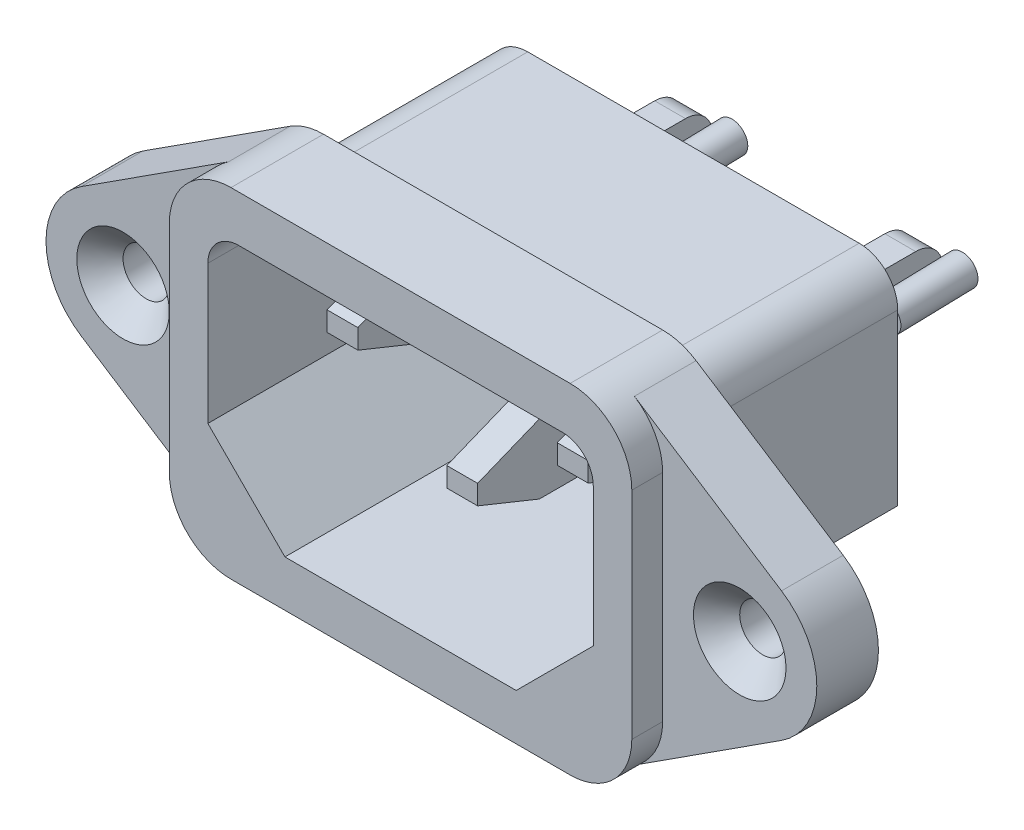
SolidWorks part; units mm, degrees
ref_plane "Front Plane" through (0, 0, 0) normal (0, 0, 1) x (1, 0, 0)
ref_plane "Top Plane" through (0, 0, 0) normal (0, 1, 0) x (1, 0, 0)
ref_plane "Right Plane" through (0, 0, 0) normal (1, 0, 0) x (0, 0, -1)
ref_plane "Plane1" through (0, 0, 0) normal (0, 0, -1) x (-1, 0, 0)
sketch "Sketch1" plane through (0, 0, 0) normal (0, 0, -1) x (-1, 0, 0)
  line L0 (-13.1694, 10.3606) -> (-22.7117, 4.2008)
  line L1 (-22.7117, -4.2008) -> (-13.1694, -10.3606)
  line L2 (-11, -11) -> (11, -11)
  line L3 (13.1694, -10.3606) -> (22.7117, -4.2008)
  line L4 (22.7117, 4.2008) -> (13.1694, 10.3606)
  line L5 (11, 11) -> (-11, 11)
  line L6 (0, 0) -> (-6.588, 0) construction
  line L7 (0, 0) -> (0, 5.2271) construction
  arc A0 (-22.7117, 4.2008) -> (-22.7117, -4.2008) centre (-20, 0) ccw
  arc A1 (-13.1694, -10.3606) -> (-11, -11) centre (-11, -7) ccw
  arc A2 (11, -11) -> (13.1694, -10.3606) centre (11, -7) ccw
  arc A3 (22.7117, -4.2008) -> (22.7117, 4.2008) centre (20, 0) ccw
  arc A4 (13.1694, 10.3606) -> (11, 11) centre (11, 7) ccw
  arc A5 (-11, 11) -> (-13.1694, 10.3606) centre (-11, 7) ccw
  point P18 (0, -11)
  point P22 (-25, 0)
  point P23 (25, 0)
  dimension "D3" = 5
  dimension "D4" = 4
  dimension "D1" = 22
  dimension "D2" = 50
  dimension "D5" = 40
extrude "Base" add sketch "Sketch1" against normal blind 4
sketch "Sketch2" plane through (0, 0, 4) normal (0, 0, 1) x (1, 0, 0)
  line L0 (11, -11) -> (-11, -11)
  line L1 (-15, -7) -> (-15, 7)
  line L2 (-11, 11) -> (11, 11)
  line L3 (15, 7) -> (15, -7)
  line L4 (-11, 11) -> (11, 11) construction
  line L5 (0, 0) -> (0, 5.1252) construction
  arc A0 (-11, -11) -> (-15, -7) centre (-11, -7) cw
  arc A1 (-15, 7) -> (-11, 11) centre (-11, 7) cw
  arc A2 (11, 11) -> (15, 7) centre (11, 7) cw
  arc A3 (15, -7) -> (11, -11) centre (11, -7) cw
  dimension "D3" = 4
  dimension "D1" = 30
  dimension "D2" = 22
extrude "Boss-Extrude2" add sketch "Sketch2" along normal blind 2
sketch "Sketch3" plane through (0, 0, 0) normal (0, 0, -1) x (-1, 0, 0)
  line L0 (13.25, -9.25) -> (-13.25, -9.25)
  line L1 (-13.25, -9.25) -> (-13.25, 9.25)
  line L2 (-13.25, 9.25) -> (13.25, 9.25)
  line L3 (13.25, 9.25) -> (13.25, -9.25)
  dimension "D1" = 26.5
  dimension "D2" = 18.5
extrude "Boss-Extrude3" add sketch "Sketch3" along normal blind 13
sketch "Sketch4" plane through (0, 0, 6) normal (0, 0, 1) x (1, 0, 0)
  line L0 (-12.5, -8) -> (12.5, -8)
  line L1 (12.5, -8) -> (12.5, 8)
  line L2 (12.5, 8) -> (-12.5, 8)
  line L3 (-12.5, 8) -> (-12.5, -8)
  line L4 (0, 4.6085) -> (0, 0) construction
  line L5 (0, 0) -> (4.1755, 0) construction
  dimension "D1" = 25
  dimension "D2" = 16
extrude "Cut-Extrude1" cut sketch "Sketch4" against normal blind 17
ref_plane "Plane2" through (1, 0, 0) normal (1, 0, 0) x (0, 0, -1)
sketch "Sketch5" plane through (1, 0, 0) normal (1, 0, 0) x (0, 0, -1)
  line L0 (2, 0.0009) -> (-3.5689, -2.2491)
  line L1 (-3.5689, -2.2491) -> (2, -4.4991)
  line L2 (2, -4.4991) -> (13, -4.4991)
  line L4 (13, 0.0009) -> (2, 0.0009)
  line L5 (13, 9.25) -> (13, -9.25) construction
  line L6 (-3.5689, -2.2491) -> (-0.3984, -2.2491) construction
  line L7 (13, 0.0009) -> (13, -0.6306)
  line L8 (13, -0.6306) -> (19.3815, -0.6306)
  line L9 (13, -4.4991) -> (13, -3.8676)
  line L10 (13, -3.8676) -> (19.3815, -3.8676)
  arc A0 (19.3815, -3.8676) -> (19.3815, -0.6306) centre (19.3815, -2.2491) ccw
  dimension "D1" = 8
  dimension "D2" = 3.2371
extrude "GND" add sketch "Sketch5" against normal blind 2
ref_plane "Plane3" through (-6.7672, 0, 0) normal (1, 0, 0) x (0, 0, -1)
sketch "Sketch6" plane through (-6.7672, 0, 0) normal (1, 0, 0) x (0, 0, -1)
  line L0 (2, 4.8652) -> (-3.5689, 2.6152)
  line L1 (-3.5689, 2.6152) -> (2, 0.3652)
  line L2 (2, 0.3652) -> (12.6657, 0.3652)
  line L3 (13, 9.25) -> (13, -9.25) construction
  line L4 (12.6657, 4.8652) -> (2, 4.8652)
  line L6 (12.6657, 4.8652) -> (12.6657, 4.3652)
  line L7 (12.6657, 4.3652) -> (19.25, 4.3652)
  line L8 (19.25, 0.8652) -> (12.6657, 0.8652)
  line L9 (12.6657, 0.8652) -> (12.6657, 0.3652)
  line L10 (-3.5689, 2.6152) -> (2.7205, 2.6152) construction
  arc A0 (19.25, 0.8652) -> (19.25, 4.3652) centre (19.25, 2.6152) ccw
  dimension "D1" = 3.5
  dimension "D2" = 8
extrude "L" add sketch "Sketch6" against normal blind 2
ref_plane "Plane4" through (8.1657, 0, 0) normal (1, 0, 0) x (0, 0, -1)
sketch "Sketch7" plane through (8.1657, 0, 0) normal (1, 0, 0) x (0, 0, -1)
  line L0 (2, 4.8652) -> (-3.5689, 2.6152)
  line L1 (-3.5689, 2.6152) -> (2, 0.3652)
  line L2 (2, 0.3652) -> (13, 0.3652)
  line L4 (13, 4.8652) -> (2, 4.8652)
  line L5 (13, 9.25) -> (13, -9.25) construction
  line L6 (13, 0.8652) -> (19.25, 0.8652) construction
  line L7 (19.25, 4.3652) -> (13, 4.3652) construction
  line L8 (13, 0.8652) -> (19.25, 0.8652)
  line L9 (19.25, 4.3652) -> (13, 4.3652)
  line L10 (13, 4.3652) -> (13, 4.8652)
  line L11 (13, 0.8652) -> (13, 0.3652)
  arc A0 (19.25, 0.8652) -> (19.25, 4.3652) centre (19.25, 2.6152) ccw construction
  arc A1 (19.25, 0.8652) -> (19.25, 4.3652) centre (19.25, 2.6152) ccw
extrude "N" add sketch "Sketch7" against normal blind 2
hole_wizard "Mount Ø3.0 (3) Diameter Hole1" positions "Sketch12" profile "Sketch11" hole size "Ø3.0" standard "ANSI Metric"
sketch "Sketch12" plane through (0, 0, 4) normal (0, 0, 1) x (1, 0, 0)
  point P0 (-20, 0)
  point P1 (20, 0)
sketch "Sketch11" plane through (-20, 0, 4) normal (1, 0, 0) x (0, -1, 0)
  line L0 (0, 0) -> (0, 25)
  line L1 (0, 25) -> (1.5, 25)
  line L2 (1.5, 25) -> (1.5, 0)
  line L5 (1.5, 0) -> (0, 0)
  line L11 (0, -6.35) -> (0, 107.95) construction
  dimension "Thru Hole Dia." = 3
  dimension "Thru Hole Depth" = 25
chamfer "Chamfer1" distance 5 angle 45 4 edges at (13.25, -9.25, -6.5) (-13.25, -9.25, -6.5) (12.5, -8, -2.5) (-12.5, -8, -2.5)
chamfer "Chamfer2" distance 1.6922 angle 68 3 edges at (0, -2.2491, 3.5689) (-7.7672, 2.6152, 3.5689) (7.1657, 2.6152, 3.5689) first distance on face at (0, -1.1241, 0.7845) first distance on face at (-7.7672, 3.7402, 0.7845) first distance on face at (7.1657, 3.7402, 0.7845)
chamfer "Chamfer3" distance 1.5 angle 45 2 edges at (-18.5, 0, 4) (21.5, 0, 4)
fillet "Fillet1" radius 2 2 edges at (12.5, 8, -2.5) (-12.5, 8, -2.5) tangent propagation no
fillet "Fillet2" radius 2.5 2 edges at (-13.25, 9.25, -6.5) (13.25, 9.25, -6.5) tangent propagation no
ref_plane "Plane5" through (0, 0.5092, -19.3515) normal (0, -0.0263, 0.9997) x (1, 0, 0)
sketch "Sketch13" plane through (0, -0.0084, -19.3651) normal (0, 0.0263, -0.9997) x (-1, 0, 0)
  line L0 (-8.1657, 4.5395) -> (-8.1657, 1.0407) construction
  line L2 (-1, -0.4546) -> (-1, -3.6905) construction
  line L3 (6.7672, 4.5395) -> (6.7672, 1.0407) construction
  line L5 (6.7672, 4.3751) -> (6.7672, 0.8757) construction
  line L6 (-8.1657, 1.0407) -> (-8.1657, 4.5395) construction
  circle A0 centre (-9.1657, 2.7901) radius 1
  circle A1 centre (5.7672, 2.7901) radius 1
  circle A2 centre (-2, -2.0725) radius 1
  point P5 (-8.1657, 2.7901)
  point P15 (-1, -2.0725)
  point P19 (6.7672, 2.7901)
  dimension "D1" = 2
extrude "Solder" add sketch "Sketch13" along normal blind 2 and the other way blind 3 separate body contours A0 | A2 | A1 | A0 | A2 | A1 region at (9.1657, 2.7808, -19.2917) region at (-5.7672, 2.7808, -19.2917) region at (2, -2.0802, -19.4196)
sketch "0_0_Point" plane through (0, 0.5618, -21.3508) normal (0, 0.0263, -0.9997) x (-1, 0, 0)
  point P0 (5.8437, 2.1813)
other "0_0" parameters "Diameter"=2, "StubLength"=2
ref_axis "Axis1" through (-5.8437, 3.0054, -31.2899) along (0, -0.0263, 0.9997)
sketch "1_0_Point" plane through (0, 0.5618, -21.3508) normal (0, 0.0263, -0.9997) x (-1, 0, 0)
  point P0 (-9.1227, 2.2592)
other "1_0" parameters "Diameter"=2, "StubLength"=2
ref_axis "Axis2" through (9.1227, 3.0832, -31.2879) along (0, -0.0263, 0.9997)
sketch "2_0_Point" plane through (0, 0.5618, -21.3508) normal (0, 0.0263, -0.9997) x (-1, 0, 0)
  point P0 (-1.8966, -2.5861)
other "2_0" parameters "Diameter"=2, "StubLength"=2
ref_axis "Axis3" through (1.8966, -1.7603, -31.4153) along (0, -0.0263, 0.9997)
ref_plane "Plane6" through (0, -5.75, 0) normal (0, 1, 0) x (1, 0, 0)
sketch "EwCable_Point" plane through (0, -5.75, 0) normal (0, 1, 0) x (1, 0, 0)
  point P0 (0, 29.7021)
other "EwCable" parameters "Diameter"=2, "StubLength"=2
ref_axis "Axis4" through (0, -15.75, -29.7021) along (0, 1, 0)
